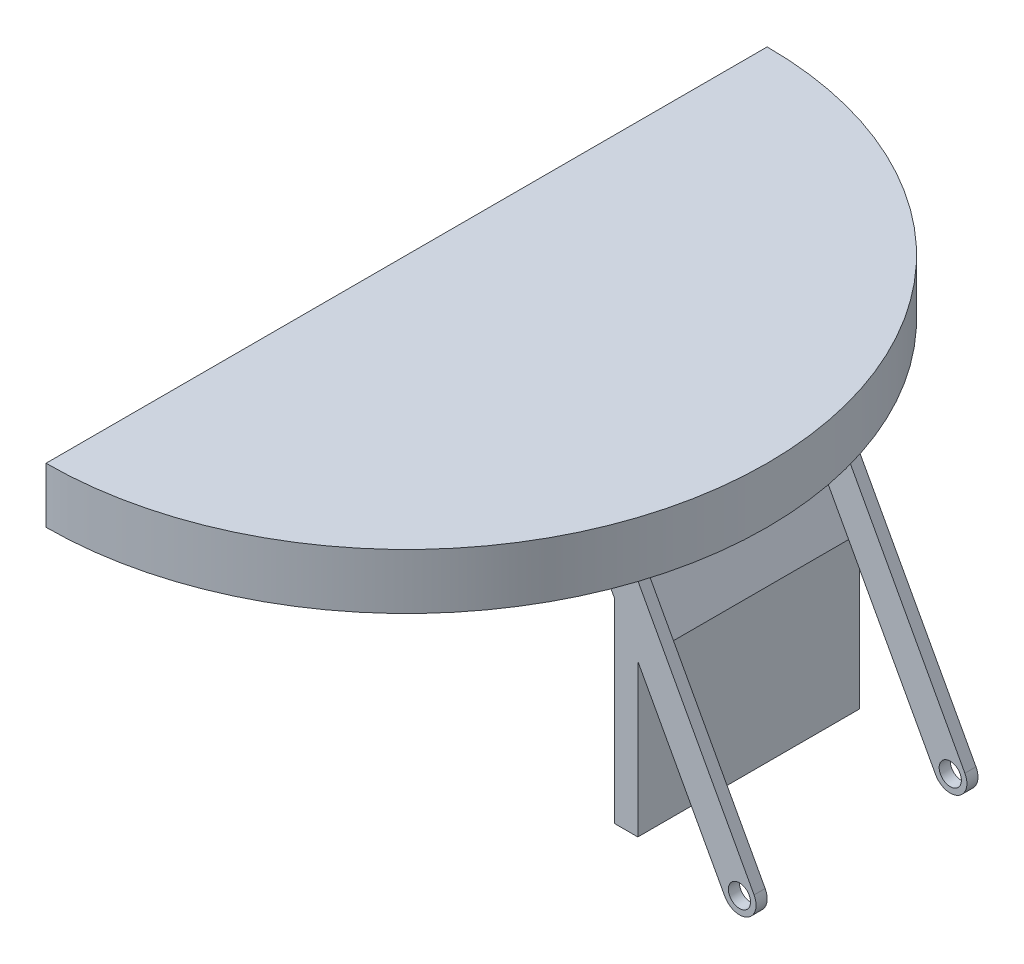
SolidWorks part; units mm, degrees
ref_plane "Ebene vorne" through (0, 0, 0) normal (0, 0, 1) x (1, 0, 0)
ref_plane "Ebene oben" through (0, 0, 0) normal (0, 1, 0) x (1, 0, 0)
ref_plane "Ebene rechts" through (0, 0, 0) normal (1, 0, 0) x (0, 0, -1)
sketch "Skizze1" plane through (0, 0, 0) normal (0, 1, 0) x (1, 0, 0)
  line L0 (0, 0) -> (0, -65)
  arc A0 (0, -65) -> (0, 0) centre (0, -32.5) ccw
  dimension "D1" = 65
extrude "Aufsatz-Linear austragen1" add sketch "Skizze1" along normal blind 5
sketch "Skizze3" plane through (0, 0, 0) normal (0, -1, 0) x (1, 0, 0)
  line L0 (30.8409, 42.5) -> (30.8409, 22.5)
  line L2 (30.8409, 22.5) -> (28.7231, 22.5)
  line L3 (28.7231, 22.5) -> (28.7231, 42.5)
  line L4 (28.7231, 42.5) -> (30.8409, 42.5)
  line L5 (32.5, 32.5) -> (29.7856, 32.5) construction
  line L6 (0, 32.5) -> (38.4387, 32.5) construction
  line L7 (0, 0) -> (0, 65) construction
  arc A2 (0, 0) -> (0, 65) centre (0, 32.5) ccw construction
  dimension "D1" = 20
extrude "Aufsatz-Linear austragen2" add sketch "Skizze3" along normal blind 20
sketch "Skizze5" plane through (0, 0.6923, 22.5) normal (0, 0, -1) x (-1, 0, 0)
  line L0 (-40, -18.875) -> (-40, -22.7457) construction
  line L1 (-41.9086, -20.6923) -> (-38.0629, -20.6923) construction
  line L2 (0, 4.3077) -> (0, -0.6923) construction
  line L4 (-32.5, -0.6923) -> (0, -0.6923) construction
  circle A0 centre (-40, -20.6923) radius 1.5
  circle A1 centre (-40, -20.6923) radius 1
  dimension "D1" = 40
  dimension "D3" = 3
  dimension "D2" = 20
extrude "Aufsatz-Linear austragen4" add sketch "Skizze5" against normal blind 20
sketch "Skizze12" plane through (0, 0, 22.5) normal (0, 0, 1) x (1, 0, 0)
  circle A0 centre (40, -20) radius 1.5
ref_plane "Ebene3" through (0, 0, 23.5) normal (0, 0, -1) x (-1, 0, 0)
sketch "Skizze14" plane through (0, 0, 23.5) normal (0, 0, -1) x (-1, 0, 0)
  circle A0 centre (-40, -20) radius 1.5
extrude "Schnitt-Linear austragen1" cut sketch "Skizze14" against normal blind 18
sketch "Skizze15" plane through (0, 0, 22.5) normal (0, 0, -1) x (-1, 0, 0)
  line L0 (-30.8409, 0) -> (-41.318, -19.2839)
  line L2 (-38.682, -20.7161) -> (-27.4265, 0)
  line L3 (-32.5, 0) -> (0, 0) construction
  line L4 (-27.4265, 0) -> (-30.8409, 0)
  circle A0 centre (-40, -20) radius 1.5 construction
  arc A1 (-38.682, -20.7161) -> (-41.318, -19.2839) centre (-40, -20) ccw
extrude "Aufsatz-Linear austragen6" add sketch "Skizze15" against normal blind 20
sketch "Skizze16" plane through (0, 0, 23.5) normal (0, 0, -1) x (-1, 0, 0)
  line L0 (-41.318, -19.2839) -> (-30.8409, 0)
  line L1 (-30.8409, 0) -> (-27.4265, 0)
  line L2 (-27.4265, 0) -> (-38.682, -20.7161)
  arc A0 (-38.682, -20.7161) -> (-41.318, -19.2839) centre (-40, -20) ccw
extrude "Schnitt-Linear austragen2" cut sketch "Skizze16" against normal blind 18
sketch "Skizze9" plane through (0, 0, 29.4822) normal (0, 0, -1) x (-1, 0, 0)
